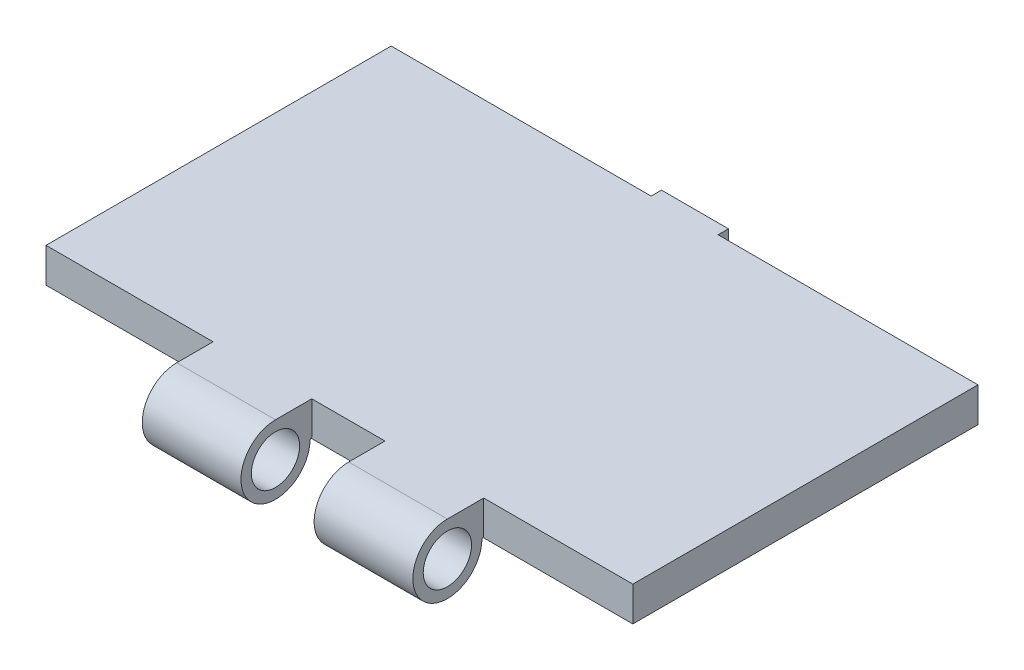
SolidWorks part; units mm, degrees
ref_plane "Plan de face" through (0, 0, 0) normal (0, 0, 1) x (1, 0, 0)
ref_plane "Plan de dessus" through (0, 0, 0) normal (0, 1, 0) x (1, 0, 0)
ref_plane "Plan de droite" through (0, 0, 0) normal (1, 0, 0) x (0, 0, -1)
sketch "Esquisse1" plane through (0, 0, 0) normal (0, 1, 0) x (1, 0, 0)
  line L1 (-42.5, 25) -> (42.5, 25)
  line L2 (-42.5, 25) -> (-42.5, -25)
  line L3 (-42.5, -25) -> (42.5, -25)
  line L4 (42.5, 25) -> (42.5, -25)
  line L5 (-42.5, 25) -> (42.5, -25) construction
  line L6 (-42.5, -25) -> (42.5, 25) construction
  point P0 (0, 0)
  dimension "D1" = 85
  dimension "D2" = 50
extrude "Boss.-Extru.1" add sketch "Esquisse1" along normal blind 5
ref_plane "Plan1" through (-18.3, 0, 0) normal (-1, 0, 0) x (0, 0, 1)
sketch "Esquisse2" plane through (-18.3, 0, 0) normal (-1, 0, 0) x (0, 0, 1)
  line L0 (25, 5) -> (25, 0) construction
  line L1 (-25, 5) -> (25, 5) construction
  line L2 (19.8455, 5) -> (25.3553, -0.0963)
  line L3 (-25, 0) -> (25, 0) construction
  line L4 (30.26, 5) -> (19.8455, 5)
  circle A0 centre (30.26, 0) radius 5
  dimension "D1" = 10
  dimension "D2" = 5.26
  dimension "D3" = 0
extrude "Boss.-Extru.2" add sketch "Esquisse2" against normal blind 14.3 contours A0 | A0 L2 region at (-18.3, 3.4873, 24.2835) region at (-18.3, 0, 30.26)
sketch "Esquisse3" plane through (-18.3, 0, 0) normal (-1, 0, 0) x (0, 0, 1)
  circle A0 centre (30.26, 0) radius 3.5
  circle A1 centre (30.26, 0) radius 5 construction
  dimension "D1" = 0
  dimension "D2" = 7
extrude "Enlèv. mat.-Extru.1" cut sketch "Esquisse3" against normal up to surface (14.3 mm away) up to face at (-4, 1.0489, 27.8896)
pattern_linear "Répétition linéaire2" count 2 spacing 24.9 along (1, 0, 0) of "Enlèv. mat.-Extru.1", "Boss.-Extru.2"
ref_plane "Plan2" through (0, 0, 0) normal (1, 0, 0) x (0, 0, -1)
sketch "Esquisse4" plane through (0, 0, 0) normal (1, 0, 0) x (0, 0, -1)
  line L1 (25, 5) -> (26.5, 5)
  line L2 (25, 5) -> (25, -4)
  line L3 (25, -4) -> (26.5, -4)
  line L4 (26.5, 5) -> (26.5, -4)
  arc A0 (25, -4) -> (25, -2.5) centre (25, -3.25) cw
  dimension "D4" = 0.75
  dimension "D1" = 1.5
  dimension "D2" = 9
  dimension "D3" = 1.5
extrude "Boss.-Extru.3" add sketch "Esquisse4" along normal blind 4.85 and the other way blind 4.85 contours A0 L2 | L3 L4 L1 L2 region at (0, -3.25, -24.6817)
